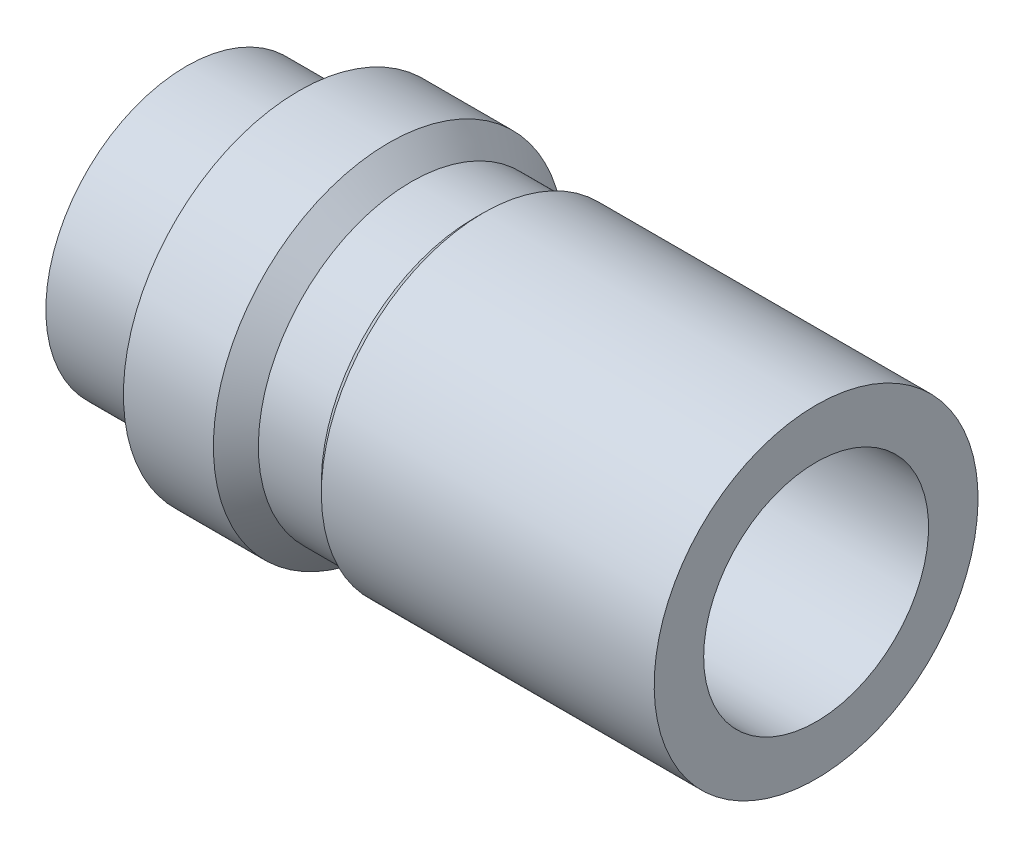
SolidWorks part; units mm, degrees
ref_plane "Front Plane" through (0, 0, 0) normal (0, 0, 1) x (1, 0, 0)
ref_plane "Top Plane" through (0, 0, 0) normal (0, 1, 0) x (1, 0, 0)
ref_plane "Right Plane" through (0, 0, 0) normal (1, 0, 0) x (0, 0, -1)
sketch "Sketch1" plane through (0, 0, 0) normal (0, 0, 1) x (1, 0, 0)
  line L0 (6.35, 7.9375) -> (6.35, 9.906)
  line L1 (6.35, 9.906) -> (11.43, 9.906)
  line L2 (11.43, 9.906) -> (12.7, 8.636)
  line L3 (12.7, 8.636) -> (16.256, 8.636)
  line L4 (16.256, 8.636) -> (16.764, 9.144)
  line L5 (16.764, 9.144) -> (35.56, 9.144)
  line L6 (35.56, 9.144) -> (35.56, 5.08)
  line L7 (35.56, 5.08) -> (35.56, 0)
  line L8 (35.56, 0) -> (0, 0)
  line L9 (31.75, 2.7681) -> (31.75, 50002.7681) construction
  line L10 (6.35, 7.9375) -> (0, 7.9375)
  line L11 (0, 7.9375) -> (0, 0)
  line L13 (57.15, 1.3357) -> (57.15, 50001.3357) construction
  dimension "D1" = 9.906
  dimension "D2" = 25.4
  dimension "D3" = 7.9375
  dimension "D4" = 6.35
  dimension "D5" = 5.08
  dimension "D6" = 1.27
  dimension "D7" = 135
  dimension "D8" = 0.762
  dimension "D9" = 3.556
  dimension "D10" = 25.4
  dimension "D11" = 5.08
  dimension "D12" = 90
  dimension "D13" = 3.81
revolve "Revolve1" add sketch "Sketch1" angle 360 about L8
hole_wizard "1/2 (0.5) Diameter Hole1" positions "Sketch2" profile "Sketch4" hole size "1/2" standard "ANSI Inch" end condition through all
sketch "Sketch2" plane through (0, 0, 0) normal (-1, 0, 0) x (0, 0, 1)
  point P0 (0, 0)
sketch "Sketch4" plane through (0, 0, 0) normal (0, 1, 0) x (0, 0, 1)
  line L0 (0, 0) -> (0, 35.56)
  line L1 (0, 35.56) -> (6.35, 35.56)
  line L2 (6.35, 35.56) -> (6.35, 0)
  line L5 (6.35, 0) -> (0, 0)
  line L11 (0, -6.35) -> (0, 107.95) construction
  dimension "Thru Hole Dia." = 12.7
  dimension "Thru Hole Depth" = 35.56
chamfer "Chamfer1" distance 0.762 angle 45 1 edges at (0, 0, 6.35)
